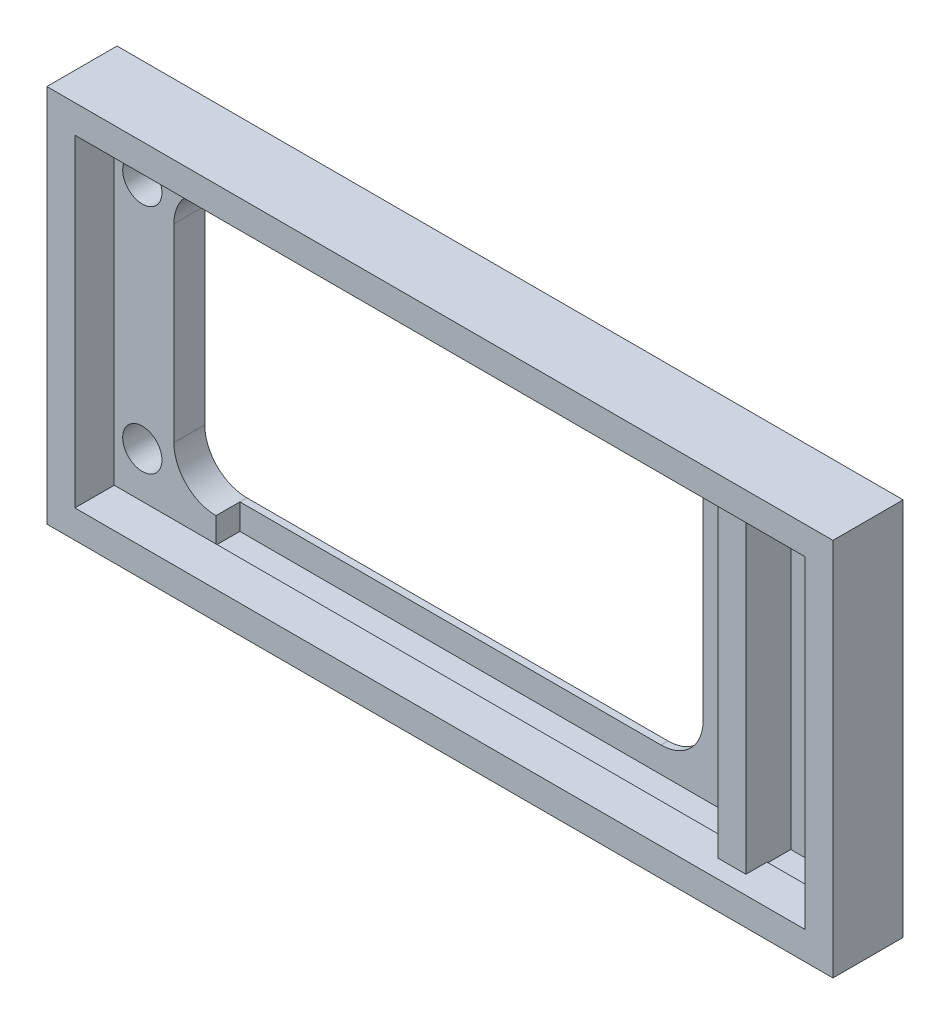
SolidWorks part; units mm, degrees
ref_plane "Front Plane" through (0, 0, 0) normal (0, 0, 1) x (1, 0, 0)
ref_plane "Top Plane" through (0, 0, 0) normal (0, 1, 0) x (1, 0, 0)
ref_plane "Right Plane" through (0, 0, 0) normal (1, 0, 0) x (0, 0, -1)
sketch "Sketch1" plane through (0, 0, 0) normal (0, 0, 1) x (1, 0, 0)
  line L1 (-26, -11.5) -> (26, -11.5)
  line L2 (-26, -11.5) -> (-26, 11.5)
  line L3 (-26, 11.5) -> (26, 11.5)
  line L4 (26, -11.5) -> (26, 11.5)
  line L5 (-26, -11.5) -> (26, 11.5) construction
  line L6 (-26, 11.5) -> (26, -11.5) construction
  line L7 (-28, -13.5) -> (28, -13.5)
  line L8 (-28, -13.5) -> (-28, 13.5)
  line L9 (-28, 13.5) -> (28, 13.5)
  line L10 (28, -13.5) -> (28, 13.5)
  line L11 (-28, -13.5) -> (28, 13.5) construction
  line L12 (-28, 13.5) -> (28, -13.5) construction
  point P0 (0, 0)
  point P6 (0, 0)
  dimension "D1" = 23
  dimension "D2" = 52
  dimension "D3" = 2
  dimension "D4" = 2
extrude "Boss-Extrude1" add sketch "Sketch1" along normal blind 5
sketch "Sketch2" plane through (0, 0, 0) normal (0, 0, -1) x (-1, 0, 0)
  line L0 (-24, 8.25) -> (-24, -8.25) construction
  line L1 (-11.25, -9.75) -> (18.75, -9.75)
  line L2 (-14.25, -6.75) -> (-14.25, 6.75)
  line L3 (-11.25, 9.75) -> (18.75, 9.75)
  line L4 (21.75, -6.75) -> (21.75, 6.75)
  line L5 (-14.25, -9.75) -> (21.75, 9.75) construction
  line L6 (-14.25, 9.75) -> (21.75, -9.75) construction
  line L7 (-28, 13.5) -> (28, 13.5) construction
  line L8 (28, -13.5) -> (-28, -13.5)
  line L9 (28, -13.5) -> (28, 13.5)
  line L10 (28, 13.5) -> (-28, 13.5)
  line L11 (-28, -13.5) -> (-28, 13.5)
  line L12 (28, -13.5) -> (-28, 13.5) construction
  line L13 (28, 13.5) -> (-28, -13.5) construction
  line L14 (-28, -13.5) -> (-28, 13.5) construction
  line L15 (26, 11.5) -> (26, -11.5) construction
  line L19 (28, 13.5) -> (28, -13.5) construction
  line L28 (28, -13.5) -> (-28, -13.5) construction
  line L29 (24, 8.25) -> (24, -8.25) construction
  arc A0 (18.75, 9.75) -> (21.75, 6.75) centre (18.75, 6.75) cw
  arc A1 (18.75, -9.75) -> (21.75, -6.75) centre (18.75, -6.75) ccw
  arc A2 (-11.25, -9.75) -> (-14.25, -6.75) centre (-11.25, -6.75) cw
  arc A3 (-14.25, 6.75) -> (-11.25, 9.75) centre (-11.25, 6.75) cw
  circle A4 centre (24, 8.25) radius 1.4
  circle A5 centre (24, -8.25) radius 1.4
  circle A6 centre (-24, 8.25) radius 1.4
  circle A7 centre (-24, -8.25) radius 1.4
  point P0 (0, 0)
  point P6 (0, 0)
  point P35 (24, 0)
  point P39 (-14.25, 0)
  point P40 (3.75, 0)
  point P44 (-24, 0)
  dimension "D3" = 3
  dimension "D4" = 2.8
  dimension "D5" = 2.8
  dimension "D6" = 2
  dimension "D7" = 2
  dimension "D8" = 36
  dimension "D9" = 16.5
  dimension "D10" = 4.25
  dimension "D11" = 4
  dimension "D12" = 16.5
  dimension "D14" = 4
  dimension "D2" = 19.5
extrude "Boss-Extrude2" add sketch "Sketch2" against normal blind 2.2
sketch "Sketch3" plane through (0, 0, 2.2) normal (0, 0, 1) x (1, 0, 0)
  line L1 (26, 11.5) -> (-18.75, 11.5)
  line L2 (26, 11.5) -> (26, -11.5719)
  line L3 (26, -11.5719) -> (-18.75, -11.5719)
  line L4 (-18.75, 11.5) -> (-18.75, -11.5719)
extrude "Cut-Extrude1" cut sketch "Sketch3" against normal blind 1.7
sketch "Sketch4" plane through (0, 0, 0.5) normal (0, 0, 1) x (1, 0, 0)
fillet "Fillet1" radius 1 1 edges at (-18.75, 10.625, 2.2)
sketch "Sketch5" plane through (0, 0, 0.5) normal (0, 0, 1) x (1, 0, 0)
  line L0 (26, 11.5) -> (-18.75, 11.5) construction
  line L1 (18.5, 11.5) -> (20.5, 11.5)
  line L2 (18.5, 11.5) -> (18.5, -11.5719)
  line L3 (18.5, -11.5719) -> (20.5, -11.5719)
  line L4 (20.5, 11.5) -> (20.5, -11.5719)
  line L5 (-18.75, -11.5719) -> (26, -11.5719) construction
  line L6 (-26, 11.5) -> (-26, -11.5) construction
  dimension "D1" = 44.5
  dimension "D2" = 2
extrude "Boss-Extrude3" add sketch "Sketch5" along normal blind 3.2
